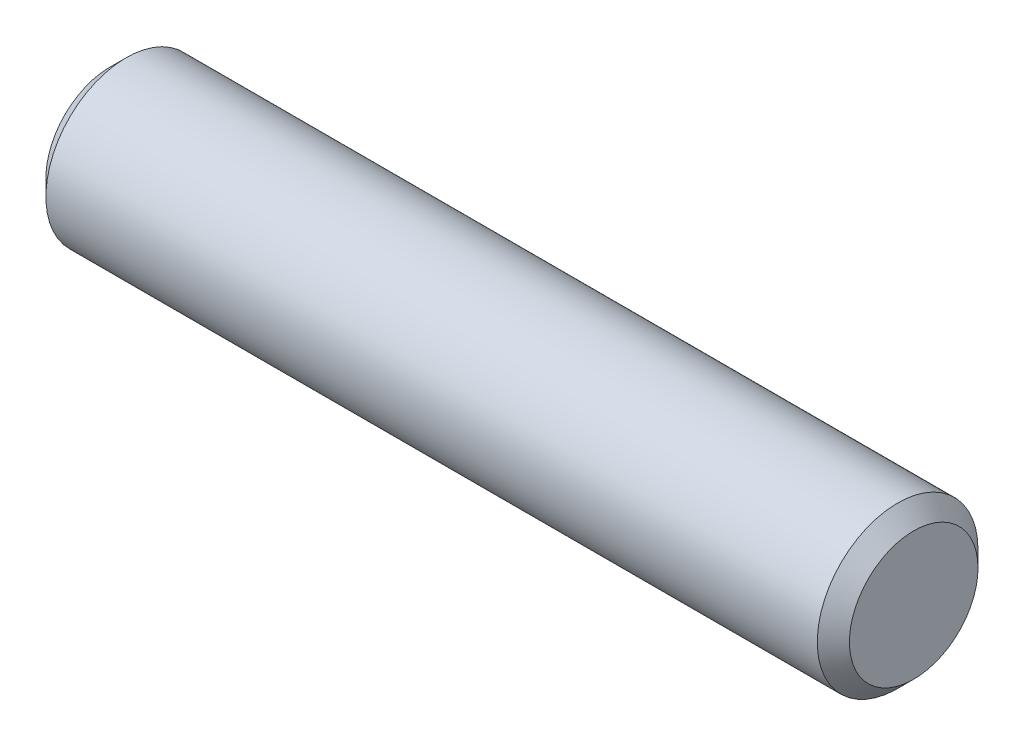
SolidWorks part; units mm, degrees
ref_plane "Front" through (0, 0, 0) normal (0, 0, 1) x (1, 0, 0)
ref_plane "Top" through (0, 0, 0) normal (0, 1, 0) x (1, 0, 0)
ref_plane "Right" through (0, 0, 0) normal (1, 0, 0) x (0, 0, -1)
sketch "Sketch1" plane through (0, 0, 0) normal (0, 0, 1) x (1, 0, 0)
  line L0 (-15.875, 0) -> (15.875, 0) construction
  line L1 (15.875, 3.175) -> (15.875, -3.175) construction
  line L2 (-15.875, 3.175) -> (-15.875, -3.175) construction
  dimension "Length" = 31.75
  dimension "Diameter" = 6.35
sketch "Sketch2" plane through (0, 0, 0) normal (1, 0, 0) x (0, 0, -1)
  circle A0 centre (0, 0) radius 3.175
extrude "Extrude1" add sketch "Sketch2" against normal up to vertex (15.875 mm away) and the other way up to vertex (15.875 mm away) up to point (-15.875, 3.175, 0) other way up to point (15.875, 3.175, 0)
chamfer "Chamfer1" distance 0.635 angle 45 2 edges at (15.875, 0, -3.175) (-15.875, 0, -3.175)
equation "\"D1@Chamfer1\" = \"Diameter@Sketch1\"*.1"
